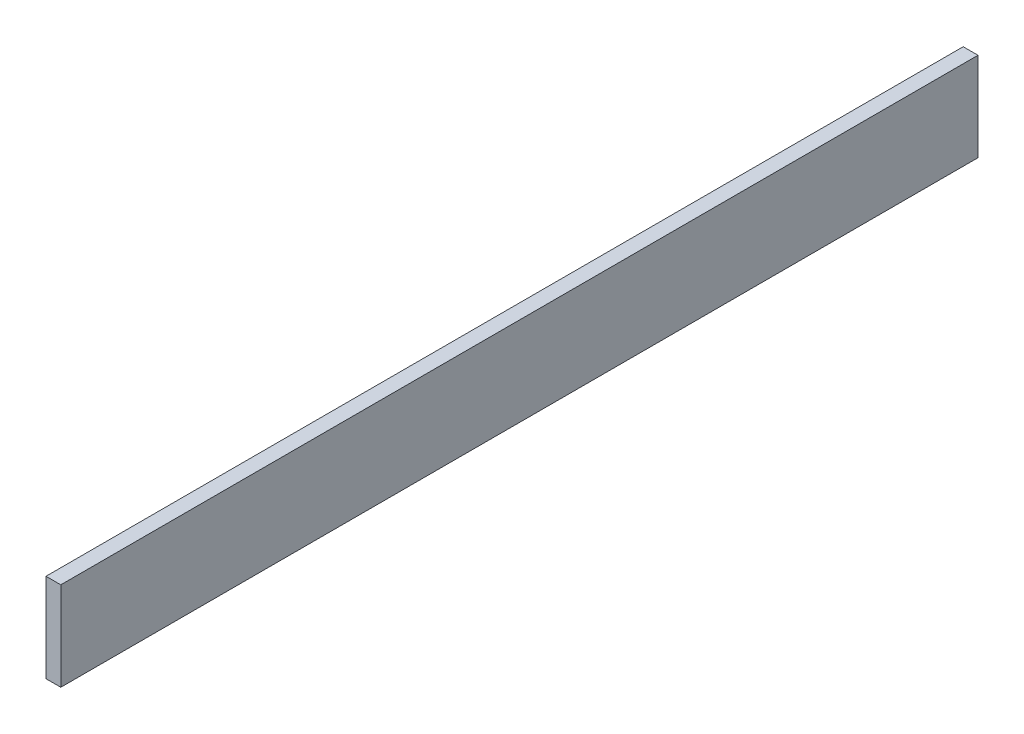
SolidWorks part; units mm, degrees
material "Acrylic (Medium-high impact)"
ref_plane "Front" through (0, 0, 0) normal (0, 0, 1) x (1, 0, 0)
ref_plane "Top" through (0, 0, 0) normal (0, 1, 0) x (1, 0, 0)
ref_plane "Right" through (0, 0, 0) normal (1, 0, 0) x (0, 0, -1)
sketch "Sketch1" plane through (0, 0, 0) normal (1, 0, 0) x (0, 0, -1)
  line L1 (-196.85, 38.1) -> (196.85, 38.1)
  line L2 (-196.85, 38.1) -> (-196.85, 0)
  line L3 (-196.85, 0) -> (196.85, 0)
  line L4 (196.85, 38.1) -> (196.85, 0)
  point P4 (0, 0)
  dimension "D1" = 393.7
  dimension "D2" = 38.1
extrude "Boss-Extrude1" add sketch "Sketch1" along normal blind 6.35
